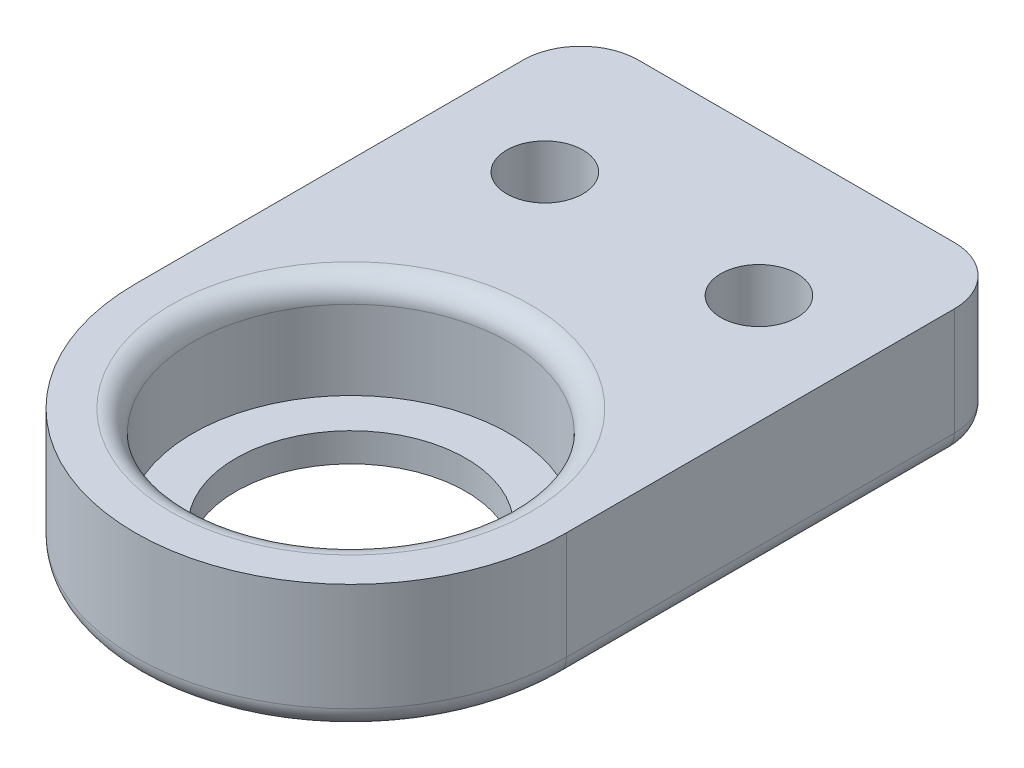
SolidWorks part; units mm, degrees
ref_plane "Front Plane" through (0, 0, 0) normal (0, 0, 1) x (1, 0, 0)
ref_plane "Top Plane" through (0, 0, 0) normal (0, 1, 0) x (1, 0, 0)
ref_plane "Right Plane" through (0, 0, 0) normal (1, 0, 0) x (0, 0, -1)
sketch "Sketch2" plane through (0, 0, 0) normal (0, 1, 0) x (1, 0, 0)
  line L1 (-15, 0) -> (15, 0)
  line L2 (-15, 0) -> (-15, 31)
  line L3 (-15, 31) -> (15, 31)
  line L4 (15, 0) -> (15, 31)
  circle A0 centre (0, 0) radius 11
  arc A1 (15, 0) -> (-15, 0) centre (0, 0) cw
  circle A2 centre (0, 0) radius 8
  point P8 (11, 0)
  point P9 (-11, 0)
  point P11 (0, 11)
  dimension "D1" = 22
  dimension "16" = 16
  dimension "D4" = 31
  dimension "30" = 30
extrude "Boss-Extrude1" add sketch "Sketch2" along normal blind 9 contours A1 L1 A0 | A0 L1 L4 L3 L2 region at (0, 0, -18.2823) region at (13, 0, 0.3354)
extrude "Boss-Extrude2" add sketch "Sketch2<3>" along normal blind 2 contours A2 L1 A0 | A2 L1 A0 region at (0, 0, -8.246) region at (9.5, 0, 0.246)
sketch "Sketch2<3>" plane through (0, 0, 0) normal (0, 1, 0) x (1, 0, 0) same geometry as "Sketch2"
hole_wizard "CSK for M5 SFHCS1" positions "3DSketch2" profile "Sketch3" countersink size "M5" standard "ANSI Metric" end condition through all
sketch3d "3DSketch2"
  line L0 (15, 0, 0) -> (15, 0, -31) construction
  line L1 (-15, 0, -31) -> (15, 0, -31) construction
  line L2 (-15, 0, 0) -> (-15, 0, -31) construction
  point P0 (7.4, 0, -21)
  point P2 (-7.5, 0, -21)
  dimension "D1" = 7.6
  dimension "D2" = 10
  dimension "D3" = 10
  dimension "D4" = 7.5
sketch "Sketch3" plane through (7.4, 0, -21) normal (1, 0, 0) x (0, 0, -1)
  line L0 (0, 0) -> (0, 9)
  line L1 (0, 9) -> (2.65, 9)
  line L2 (2.65, 9) -> (2.65, 2.95)
  line L3 (2.65, 2.95) -> (5.6, 0)
  line L5 (5.6, 0) -> (0, 0)
  line L6 (-2.65, 2.95) -> (-5.6, 0) construction
  line L11 (0, -6.35) -> (0, 107.95) construction
  dimension "Thru Hole Dia." = 5.3
  dimension "Thru Hole Depth" = 9
  dimension "Near C'Sink Dia." = 11.2
  dimension "Near C'Sink Angle" = 90
fillet "Fillet1" radius 4 2 edges at (-15, 4.5, -31) (15, 4.5, -31)
fillet "Fillet2" radius 1.5 7 edges at (0, 0, 15) (-15, 0, -13.5) (-13.8284, 0, -29.8284) (0, 0, -31) (13.8284, 0, -29.8284) (0, 9, 11) (15, 0, -13.5)
